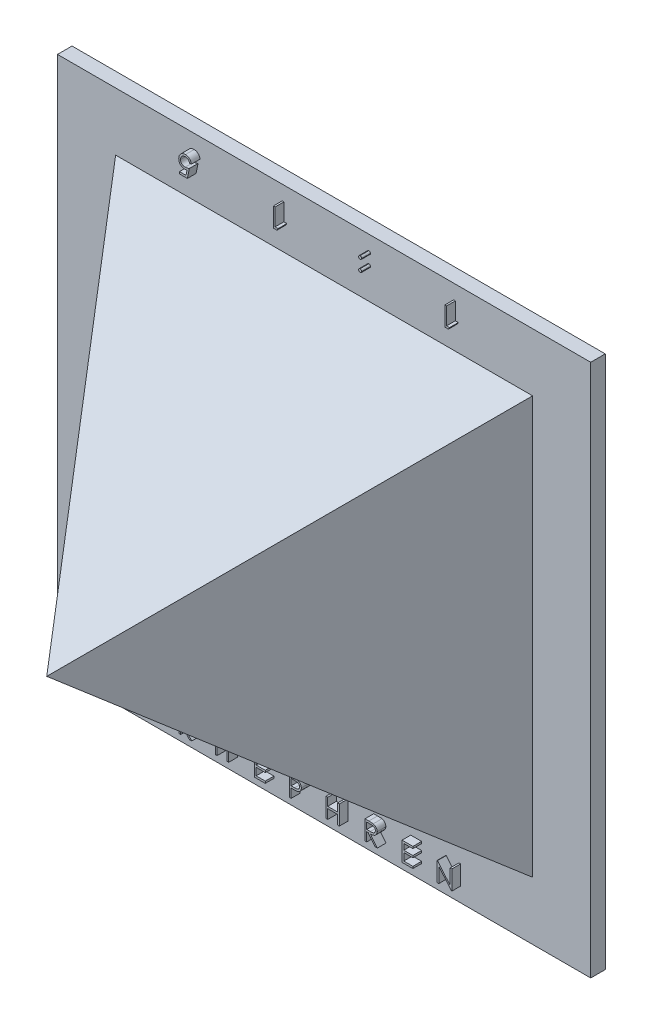
SolidWorks part; units mm, degrees
ref_plane "Plan de face" through (0, 0, 0) normal (0, 0, 1) x (1, 0, 0)
ref_plane "Plan de dessus" through (0, 0, 0) normal (0, 1, 0) x (1, 0, 0)
ref_plane "Plan de droite" through (0, 0, 0) normal (1, 0, 0) x (0, 0, -1)
sketch "Esquisse1" plane through (0, 0, 0) normal (0, 0, 1) x (1, 0, 0)
  line L1 (0, 0) -> (143.44, 0)
  line L2 (0, 0) -> (0, 143.44)
  line L3 (0, 143.44) -> (143.44, 143.44)
  line L4 (143.44, 0) -> (143.44, 143.44)
  dimension "D1" = 143.44
extrude "Boss.-Extru.1" add sketch "Esquisse1" along normal blind 95.9 draft 36.93
sketch "Esquisse3" plane through (0, 0, 0) normal (0, 0, -1) x (-1, 0, 0)
  line L8 (20, -20) -> (20, 163.44)
  line L9 (20, 163.44) -> (-163.44, 163.44)
  line L10 (-163.44, 163.44) -> (-163.44, -20)
  line L11 (-163.44, -20) -> (20, -20)
  line L12 (20, -20) -> (20, 163.44)
  line L13 (20, 163.44) -> (-163.44, 163.44)
  line L14 (-163.44, 163.44) -> (-163.44, -20)
  line L15 (-163.44, -20) -> (20, -20)
  dimension "D1" = 20
extrude "Boss.-Extru.3" add sketch "Esquisse3" along normal blind 5 separate body
sketch "Esquisse2" plane through (0, 0, -5) normal (0, 0, -1) x (-1, 0, 0)
  line L0 (0, 0) -> (-143.44, 0) construction
  line L1 (0, 143.44) -> (0, 0) construction
  circle A0 centre (-71.72, 71.72) radius 23.25
  point P5 (-71.72, 0)
  point P8 (0, 71.72)
  dimension "D1" = 46.5
extrude "Boss.-Extru.2" add sketch "Esquisse2" along normal blind 30
sketch "Esquisse4" plane through (0, 0, 0) normal (0, 0, 1) x (1, 0, 0)
  line L0 (23.9145, -15) -> (119.5255, -15) construction
  line L1 (24.2886, 158.44) -> (119.1514, 158.44) construction
  line L2 (0, 0) -> (143.44, 0) construction
  line L3 (163.44, -20) -> (-20, -20) construction
  line L5 (-20, 163.44) -> (163.44, 163.44) construction
  line L6 (143.44, 143.44) -> (0, 143.44) construction
  text T0 "KHEPHREN" font "Century Gothic" height in points 25
  text T1 "1:15" font "Century Gothic" height in points 25
  point P6 (71.72, 0)
  point P7 (71.72, -15)
  point P12 (71.72, 143.44)
  point P13 (71.72, 158.44)
  dimension "D1" = 5
  dimension "D2" = 5
extrude "Boss.-Extru.4" add sketch "Esquisse4" along normal blind 3
